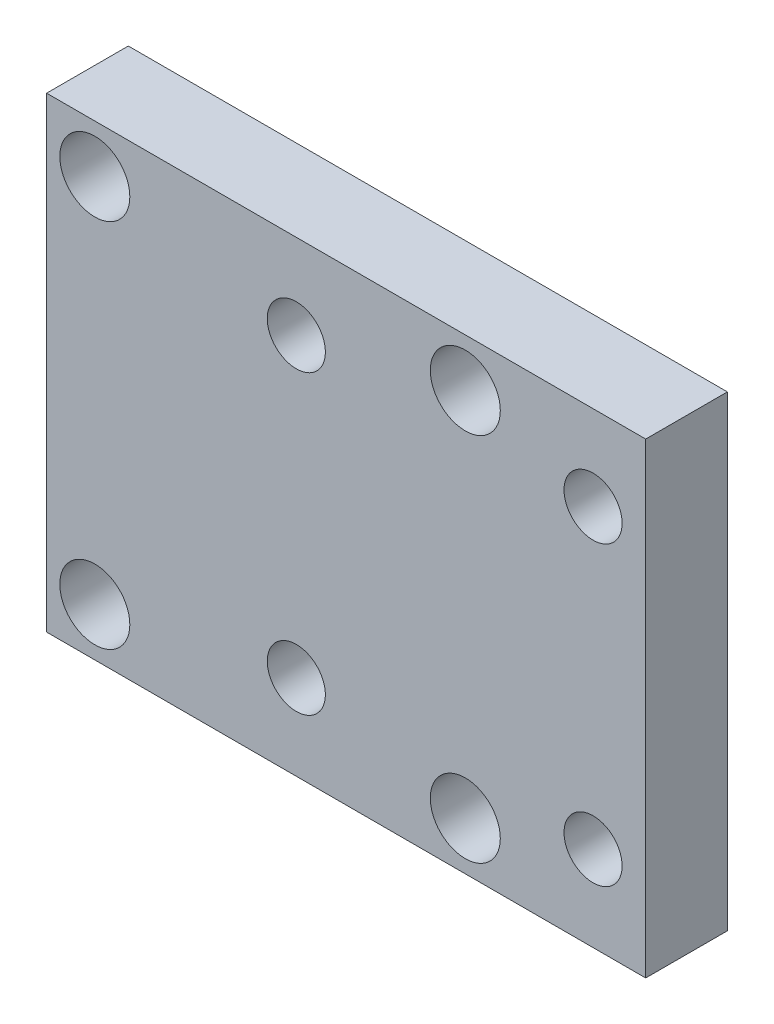
SolidWorks part; units mm, degrees
ref_plane "Front Plane" through (0, 0, 0) normal (0, 0, 1) x (1, 0, 0)
ref_plane "Top Plane" through (0, 0, 0) normal (0, 1, 0) x (1, 0, 0)
ref_plane "Right Plane" through (0, 0, 0) normal (1, 0, 0) x (0, 0, -1)
sketch "Sketch1" plane through (0, 0, 0) normal (0, 0, 1) x (1, 0, 0)
  line L1 (-14.09, 0) -> (-65.43, 0)
  line L2 (-14.09, 0) -> (-14.09, -40)
  line L3 (-14.09, -40) -> (-65.43, -40)
  line L4 (-65.43, 0) -> (-65.43, -40)
  dimension "D1" = 51.34
  dimension "D2" = 40
extrude "Boss-Extrude1" add sketch "Sketch1" along normal blind 7
sketch "Sketch2" plane through (0, 0, 0) normal (0, 0, 1) x (1, 0, 0)
  line L4 (-65.43, 0) -> (-65.43, -40) construction
  line L6 (-65.43, -40) -> (-14.09, -40) construction
  circle A6 centre (-61.3, -35.875) radius 2
  circle A7 centre (-29.55, -35.875) radius 2
  circle A8 centre (-29.55, -4.125) radius 2
  circle A9 centre (-61.3, -4.125) radius 2
  dimension "D1" = 31.75
  dimension "D2" = 31.75
  dimension "D3" = 4.13
  dimension "D4" = 4
  dimension "D5" = 4.125
  dimension "D6" = 2
  dimension "D7" = 2
extrude "Cut-Extrude2" cut sketch "Sketch2" along normal through all
sketch "Sketch8" plane through (0, 0, 7) normal (0, 0, 1) x (1, 0, 0)
  circle A0 centre (-61.3, -4.125) radius 3
  circle A3 centre (-29.55, -4.125) radius 3
  circle A4 centre (-29.55, -35.875) radius 3
  circle A5 centre (-61.3, -35.875) radius 3
  dimension "D1" = 6
  dimension "D2" = 2
  dimension "D3" = 2
extrude "Cut-Extrude6" cut sketch "Sketch8" against normal blind 6
sketch "Sketch9" plane through (0, 0, 7) normal (0, 0, 1) x (1, 0, 0)
  line L0 (-18.6008, -7.27) -> (-18.6008, -43.6541) construction
  line L1 (-18.6008, -7.27) -> (-44.0308, -7.27) construction
  line L2 (-44.0308, -7.27) -> (-44.0308, -32.7) construction
  line L3 (-44.0308, -32.7) -> (-18.6008, -32.7) construction
  circle A0 centre (-44.0308, -7.27) radius 2.49
  circle A1 centre (-18.6008, -7.27) radius 2.49
  circle A2 centre (-44.0308, -32.7) radius 2.49
  circle A3 centre (-18.6008, -32.7) radius 2.49
  dimension "D2" = 25.43
  dimension "D3" = 25.43
  dimension "D4" = 2
  dimension "D5" = 2
extrude "Cut-Extrude7" cut sketch "Sketch9" against normal up to surface (7 mm away) up to face at (-27.55, -4.125, 0)
equation "\"hole_screw_1_4_20\"= 6"
equation "\"inch\"=25.43"
